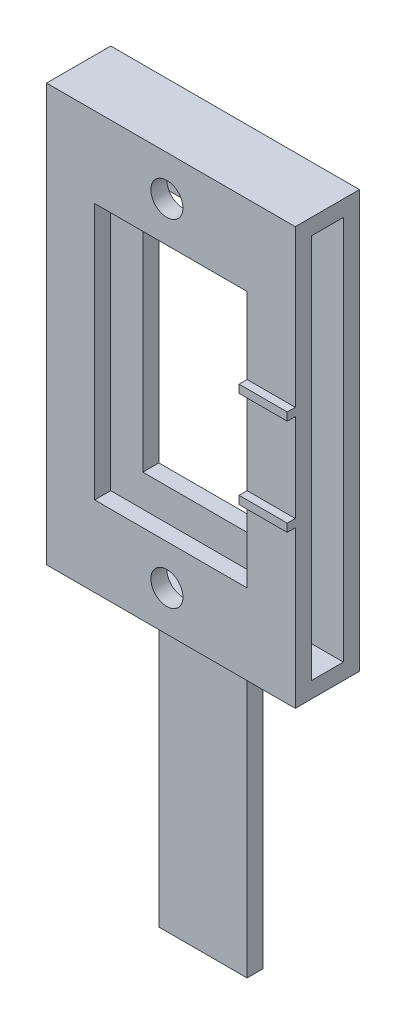
SolidWorks part; units mm, degrees
ref_plane "Front Plane" through (0, 0, 0) normal (0, 0, 1) x (1, 0, 0)
ref_plane "Top Plane" through (0, 0, 0) normal (0, 1, 0) x (1, 0, 0)
ref_plane "Right Plane" through (0, 0, 0) normal (1, 0, 0) x (0, 0, -1)
sketch "Sketch1" plane through (0, 0, 0) normal (0, 0, 1) x (1, 0, 0)
  line L1 (2.75, -19.65) -> (-2.75, -19.65)
  line L2 (2.75, -19.65) -> (2.75, 19.65)
  line L3 (2.75, 19.65) -> (-2.75, 19.65)
  line L4 (-2.75, -19.65) -> (-2.75, 19.65)
  line L5 (2.75, -19.65) -> (-2.75, 19.65) construction
  line L6 (2.75, 19.65) -> (-2.75, -19.65) construction
  point P0 (0, 0)
  dimension "D1" = 39.3
  dimension "D2" = 5.5
extrude "Boss-Extrude1" add sketch "Sketch1" along normal blind 1
sketch "Sketch2" plane through (0, 0, 1) normal (0, 0, 1) x (1, 0, 0)
  line L0 (-2.75, 19.65) -> (-2.75, -19.65) construction
  line L1 (2.75, 19.65) -> (-2.75, 19.65) construction
  line L3 (-0.25, 15.9) -> (-2.75, 15.9)
  line L4 (-0.25, 15.9) -> (-0.25, 12.9)
  line L5 (-0.25, 12.9) -> (-2.75, 12.9)
  line L6 (-2.75, 15.9) -> (-2.75, 12.9)
  line L7 (-0.25, 9.9) -> (-2.75, 9.9)
  line L8 (-0.25, 9.9) -> (-0.25, 6.9)
  line L9 (-0.25, 6.9) -> (-2.75, 6.9)
  line L10 (-2.75, 9.9) -> (-2.75, 6.9)
  circle A0 centre (-0.25, 14.4) radius 1.5
  circle A1 centre (-0.25, 8.4) radius 1.5
  point P16 (0, 0)
  dimension "D1" = 3
  dimension "D5" = 3
  dimension "D2" = 2.5
  dimension "D3" = 5.25
  dimension "D4" = 2.5
  dimension "D6" = 11.25
  dimension "D7" = 3
  dimension "D8" = 3
sketch "Sketch3" plane through (0, 0, 1) normal (0, 0, 1) x (1, 0, 0)
  line L1 (7.75, -1.6) -> (-7.75, -1.6)
  line L2 (7.75, -1.6) -> (7.75, 24.4)
  line L3 (7.75, 24.4) -> (-7.75, 24.4)
  line L4 (-7.75, -1.6) -> (-7.75, 24.4)
  line L5 (-2.75, 19.65) -> (-2.75, -19.65) construction
  line L7 (2.75, -19.65) -> (2.75, 19.65) construction
  point P6 (2.75, 4.8644)
  point P7 (2.75, 4.8644)
  point P8 (0, 0)
  point P9 (2.75, 4.8644)
  point P10 (2.75, 4.8644)
  point P13 (2.75, 4.8644)
  point P14 (2.75, 4.8644)
  point P15 (2.75, 4.8644)
  point P16 (2.75, 4.8644)
  point P17 (2.75, 4.8644)
  point P18 (2.75, 4.8644)
  dimension "D1" = 5
  dimension "D2" = 10
  dimension "D3" = 10
  dimension "D4" = 5
extrude "Boss-Extrude5" add sketch "Sketch3" against normal mid plane 4
extrude "Boss-Extrude6" add sketch "Sketch3<2>" along normal blind 2
sketch "Sketch3<2>" plane through (0, 0, 1) normal (0, 0, 1) x (1, 0, 0) same geometry as "Sketch3"
sketch "Sketch10" plane through (7.75, 0, 0) normal (1, 0, 0) x (0, 0, -1)
  line L0 (-3, -1.6) -> (-3, 24.4) construction
  line L1 (-2, 23.4) -> (0, 23.4)
  line L2 (-2, 23.4) -> (-2, -0.6)
  line L3 (-2, -0.6) -> (0, -0.6)
  line L4 (0, 23.4) -> (0, -0.6)
  line L5 (1, -1.6) -> (1, 24.4) construction
  line L6 (1, -1.6) -> (-3, -1.6) construction
  line L7 (1, 24.4) -> (-3, 24.4) construction
  dimension "D1" = 1
  dimension "D2" = 1
  dimension "D3" = 1
  dimension "D4" = 1
extrude "Cut-Extrude5" cut sketch "Sketch10" against normal blind 14.5 and the other way through all
sketch "Sketch11" plane through (0, 0, 3) normal (0, 0, 1) x (1, 0, 0)
  line L0 (7.75, 24.4) -> (-7.75, 24.4) construction
  line L1 (-4.75, 19.4) -> (4.75, 19.4)
  line L2 (-4.75, 19.4) -> (-4.75, 3.4)
  line L3 (-4.75, 3.4) -> (4.75, 3.4)
  line L4 (4.75, 19.4) -> (4.75, 3.4)
  line L5 (-7.75, -1.6) -> (7.75, -1.6) construction
  line L6 (-7.75, 24.4) -> (-7.75, -1.6) construction
  line L7 (7.75, -1.6) -> (7.75, 24.4) construction
  dimension "D1" = 5
  dimension "D2" = 5
  dimension "D3" = 3
  dimension "D4" = 3
extrude "Cut-Extrude7" cut sketch "Sketch11" against normal blind 10
sketch "Sketch12" plane through (0, 0, 3) normal (0, 0, 1) x (1, 0, 0)
  line L1 (-0.25, 15.9) -> (-0.25, 12.9) construction
  line L2 (-0.25, 9.9) -> (-0.25, 6.9) construction
  circle A0 centre (-0.25, 21.9) radius 0.9809
  circle A1 centre (-0.25, 0.9) radius 0.958
  point P6 (0, 0)
  dimension "D1" = 7.5
  dimension "D2" = 0
  dimension "D3" = 0
  dimension "D4" = 7.5
hole_wizard "Ø2.0mm Dowel Hole1" positions "3DSketch5" profile "Sketch13" hole size "Ø2.0" standard "ANSI Metric" end condition up to next
sketch3d "3DSketch5"
  point P0 (-0.25, 21.9, 3)
  point P3 (-0.25, 0.9, 3)
sketch "Sketch13" plane through (-0.25, 21.9, 3) normal (1, 0, 0) x (0, -1, 0)
  line L0 (0, 0) -> (0, 1)
  line L1 (0, 1) -> (1, 1)
  line L2 (1, 1) -> (1, 0)
  line L5 (1, 0) -> (0, 0)
  line L11 (0, -6.35) -> (0, 107.95) construction
  dimension "Thru Hole Dia." = 2
  dimension "Thru Hole Depth" = 1
sketch "Sketch15" plane through (0, 0, 3) normal (0, 0, 1) x (1, 0, 0)
  line L0 (4.75, 3.4) -> (4.75, 19.4) construction
  line L1 (4.75, 14.65) -> (7.75, 14.65)
  line L2 (4.75, 14.65) -> (4.75, 14.15)
  line L3 (4.75, 14.15) -> (7.75, 14.15)
  line L4 (7.75, 14.65) -> (7.75, 14.15)
  line L5 (4.75, 14.65) -> (7.75, 14.15) construction
  line L6 (4.75, 14.15) -> (7.75, 14.65) construction
  line L7 (7.75, -1.6) -> (7.75, 24.4) construction
  line L9 (4.75, 8.65) -> (7.75, 8.65)
  line L10 (4.75, 8.65) -> (4.75, 8.15)
  line L11 (4.75, 8.15) -> (7.75, 8.15)
  line L12 (7.75, 8.65) -> (7.75, 8.15)
  line L13 (4.75, 8.65) -> (7.75, 8.15) construction
  line L14 (4.75, 8.15) -> (7.75, 8.65) construction
  point P0 (6.25, 14.4)
  point P5 (4.75, 14.4)
  point P10 (6.25, 8.4)
  point P14 (6.222, 14.3664)
  dimension "D1" = 0
  dimension "D2" = 0
  dimension "D3" = 0.5
  dimension "D4" = 0.25
  dimension "D5" = 0.5
  dimension "D6" = 0
  dimension "D7" = 0
  dimension "D8" = 0.25
extrude "Boss-Extrude7" add sketch "Sketch15" along normal blind 0.5
